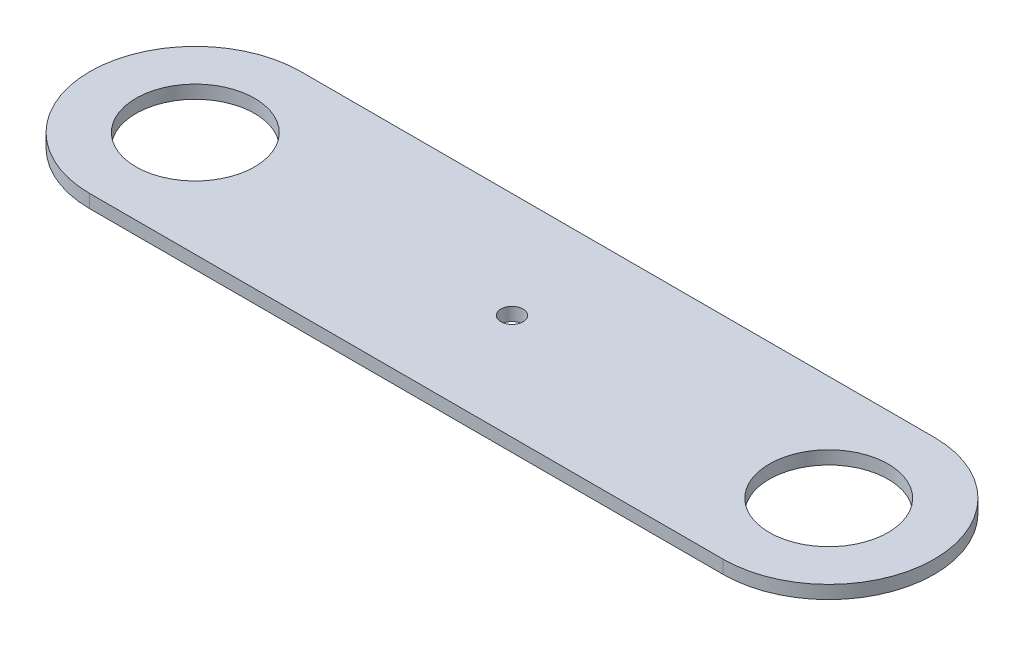
SolidWorks part; units mm, degrees
ref_plane "Front" through (0, 0, 0) normal (0, 0, 1) x (1, 0, 0)
ref_plane "Top" through (0, 0, 0) normal (0, 1, 0) x (1, 0, 0)
ref_plane "Right" through (0, 0, 0) normal (1, 0, 0) x (0, 0, -1)
sketch "Sketch1" plane through (0, 0, 0) normal (0, 1, 0) x (1, 0, 0)
  line L0 (0, 0) -> (152.4, 0) construction
  line L1 (0, 0) -> (152.4, 0) construction
  line L2 (0, 25.4) -> (152.4, 25.4)
  line L3 (0, -25.4) -> (152.4, -25.4)
  circle A0 centre (0, 0) radius 14.2875
  circle A1 centre (152.4, 0) radius 14.2875
  arc A2 (0, 25.4) -> (0, -25.4) centre (0, 0) ccw
  arc A3 (152.4, -25.4) -> (152.4, 25.4) centre (152.4, 0) ccw
  point P5 (76.2, 0)
  point P10 (76.2, -25.4)
  dimension "D1" = 28.575
  dimension "D2" = 28.575
  dimension "D3" = 152.4
  dimension "D4" = 50.8
extrude "Boss-Extrude1" add sketch "Sketch1" along normal blind 3.175
sketch "Sketch2" plane through (0, 3.175, 0) normal (0, 1, 0) x (1, 0, 0)
  line L0 (0, 0) -> (152.4, 0) construction
  circle A0 centre (76.2, 0) radius 2.667
  dimension "D1" = 5.334
extrude "Cut-Extrude1" cut sketch "Sketch2" against normal up to next
sketch "Sketch3" plane through (0, 3.175, 0) normal (0, 1, 0) x (1, 0, 0)
  line L0 (152.4, 0) -> (177.8, 0) construction
  line L1 (0, 0) -> (-25.4, 0) construction
  arc A0 (152.4, -25.4) -> (152.4, 25.4) centre (152.4, 0) ccw construction
  arc A1 (0, 25.4) -> (0, -25.4) centre (0, 0) ccw construction
